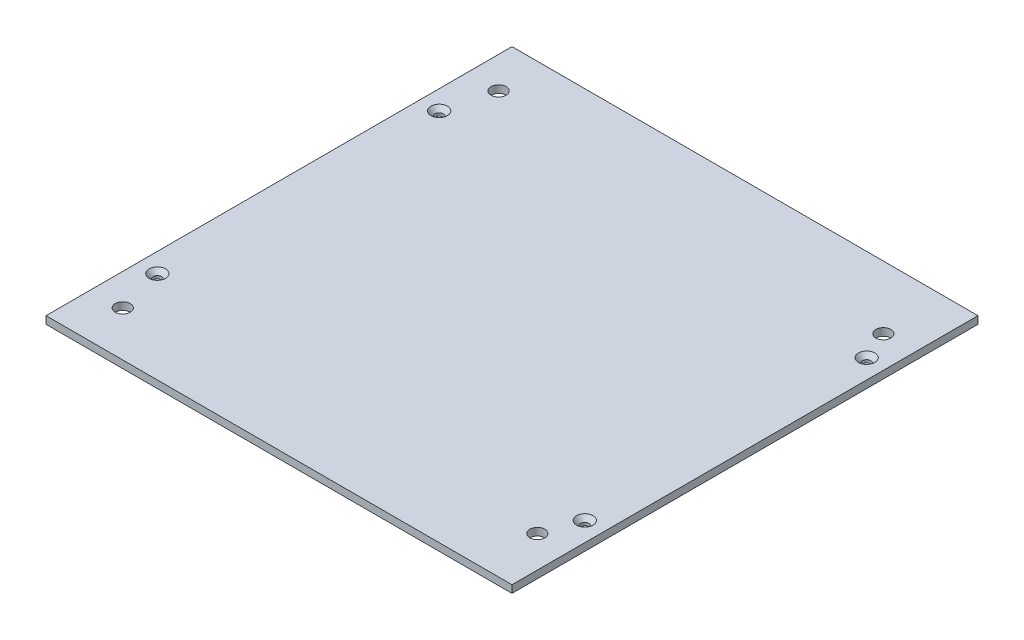
SolidWorks part; units mm, degrees
material "6061-T4 (SS)"
ref_plane "Front Plane" through (0, 0, 0) normal (0, 0, 1) x (1, 0, 0)
ref_plane "Top Plane" through (0, 0, 0) normal (0, 1, 0) x (1, 0, 0)
ref_plane "Right Plane" through (0, 0, 0) normal (1, 0, 0) x (0, 0, -1)
sketch "Sketch1" plane through (0, 0, 0) normal (0, 1, 0) x (1, 0, 0)
  line L1 (0, 0) -> (99.2004, 0)
  line L2 (0, 0) -> (0, 99.2004)
  line L3 (0, 99.2004) -> (99.2004, 99.2004)
  line L4 (99.2004, 0) -> (99.2004, 99.2004)
  dimension "D1" = 99.2004
  dimension "D2" = 99.2004
extrude "Boss-Extrude1" add sketch "Sketch1" along normal blind 1.6002
sketch "Sketch3" plane through (0, 1.6002, 0) normal (0, 1, 0) x (1, 0, 0)
  line L0 (0, 0) -> (1.6002, 0) construction
  line L1 (0, 0) -> (99.2004, 0) construction
  line L2 (1.6002, 0) -> (1.6002, 99.2004) construction
  line L3 (99.2004, 99.2004) -> (0, 99.2004) construction
  line L4 (0, 97.6002) -> (1.6002, 97.6002) construction
  line L5 (0, 99.2004) -> (0, 0) construction
  line L6 (1.6002, 97.6002) -> (97.6002, 97.6002) construction
  line L7 (97.6002, 97.6002) -> (97.6002, 99.2004) construction
  line L8 (97.6002, 97.6002) -> (97.6002, 0) construction
  line L9 (99.2004, 0) -> (99.2004, 99.2004) construction
  line L10 (49.6002, 97.6002) -> (49.6002, 49.6002) construction
  line L11 (95.1002, 49.6002) -> (4.1002, 49.6002) construction
  line L12 (4.1002, 49.6002) -> (4.1002, 79.6002) construction
  line L13 (4.1002, 49.6002) -> (4.1002, 19.6002) construction
  line L14 (95.1002, 49.6002) -> (95.1002, 19.6002) construction
  line L15 (95.1002, 49.6002) -> (95.1002, 79.6002) construction
  line L16 (1.6002, 1.6002) -> (97.6002, 1.6002) construction
  line L17 (49.6002, 49.6002) -> (49.6002, 1.6002) construction
  dimension "D1" = 1.6002
  dimension "D2" = 1.6002
  dimension "D3" = 1.6002
  dimension "D4" = 2.5
  dimension "D5" = 30
  dimension "D6" = 1.6002
hole_wizard "CSK for #0 Flat Head Socket Cap Screw1" positions "Sketch4" profile "Sketch5" countersink size "#0" standard "ANSI Inch" end condition through all
sketch "Sketch4" plane through (0, 1.6002, 0) normal (0, 1, 0) x (1, 0, 0)
  point P0 (4.1002, 79.6002)
  point P3 (4.1002, 19.6002)
  point P6 (95.1002, 19.6002)
  point P9 (95.1002, 79.6002)
sketch "Sketch5" plane through (4.1002, 1.6002, -79.6002) normal (1, 0, 0) x (0, 0, 1)
  line L0 (0, 0) -> (0, 1.6002)
  line L1 (0, 1.6002) -> (0.889, 1.6002)
  line L2 (0.889, 1.6002) -> (0.889, 0.9935)
  line L3 (0.889, 0.9935) -> (1.7526, 0)
  line L5 (1.7526, 0) -> (0, 0)
  line L6 (-0.889, 0.9935) -> (-1.7526, 0) construction
  line L11 (0, -6.35) -> (0, 107.95) construction
  dimension "Thru Hole Dia." = 1.778
  dimension "Thru Hole Depth" = 1.6002
  dimension "Near C'Sink Dia." = 3.5052
  dimension "Near C'Sink Angle" = 82
sketch "Sketch7" plane through (0, 1.6002, 0) normal (0, 1, 0) x (1, 0, 0)
  circle A0 centre (6.7377, 9.5952) radius 1.6
  circle A1 centre (6.7377, 89.6052) radius 1.6
  circle A2 centre (92.4627, 85.7952) radius 1.6
  circle A3 centre (92.4627, 12.1352) radius 1.6
  circle A4 centre (92.4627, 12.1352) radius 1.6 construction
  circle A5 centre (6.7377, 9.5952) radius 1.6 construction
  circle A6 centre (6.7377, 89.6052) radius 1.6 construction
  circle A7 centre (92.4627, 85.7952) radius 1.6 construction
extrude "Cut-Extrude1" cut sketch "Sketch7" against normal blind 10
sketch "Sketch8" [suppressed] plane through (0, 1.6002, 0) normal (0, 1, 0) x (1, 0, 0)
  circle A0 centre (92.4627, 9.5952) radius 1.6
  circle A1 centre (92.4627, 89.6052) radius 1.6
  circle A2 centre (6.7377, 85.7952) radius 1.6
  circle A3 centre (6.7377, 12.1352) radius 1.6
  circle A4 centre (6.7377, 12.1352) radius 1.6 construction
  circle A5 centre (92.4627, 9.5952) radius 1.6 construction
  circle A6 centre (92.4627, 89.6052) radius 1.6 construction
  circle A7 centre (6.7377, 85.7952) radius 1.6 construction
extrude "Cut-Extrude2" [suppressed] cut sketch "Sketch8" against normal blind 10
